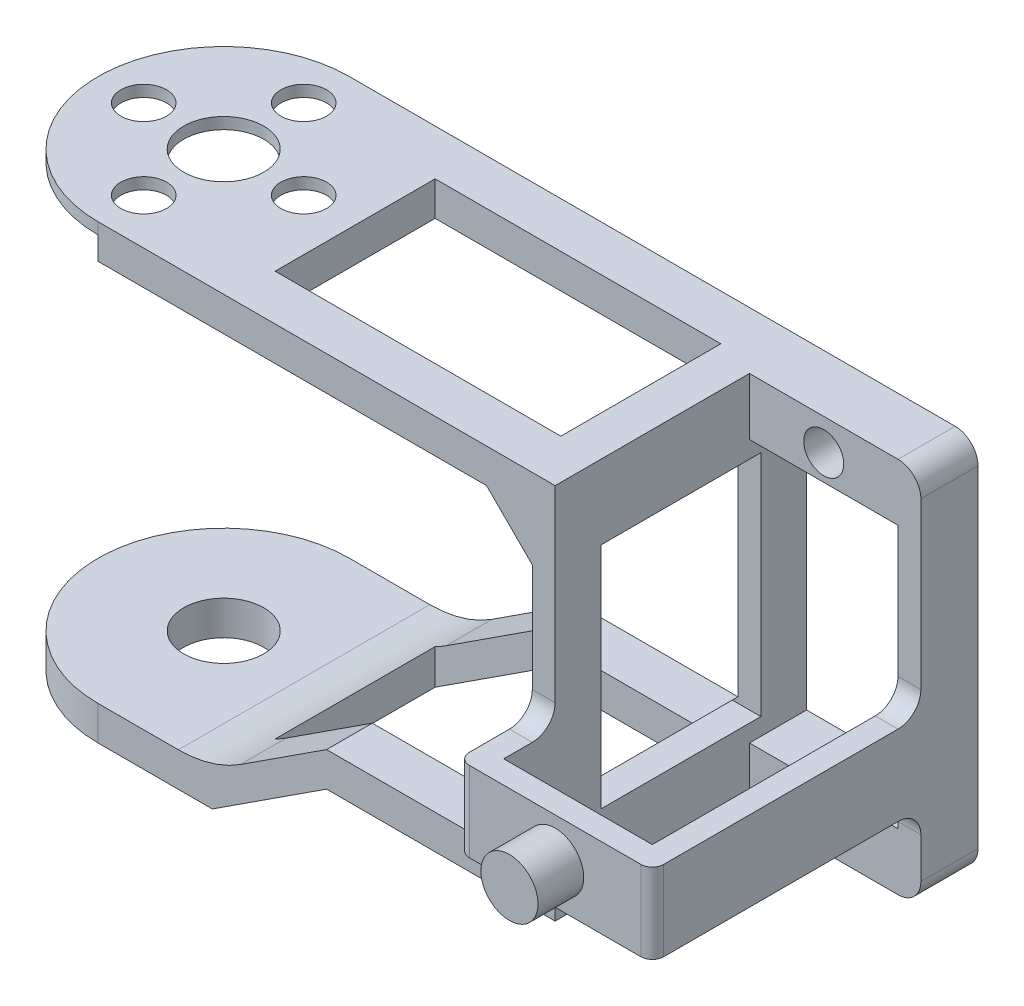
SolidWorks part; units mm, degrees
ref_plane "前视基准面" through (0, 0, 0) normal (0, 0, 1) x (1, 0, 0)
ref_plane "上视基准面" through (0, 0, 0) normal (0, 1, 0) x (1, 0, 0)
ref_plane "右视基准面" through (0, 0, 0) normal (1, 0, 0) x (0, 0, -1)
sketch "草图1" plane through (0, 0, 0) normal (0, 1, 0) x (1, 0, 0)
  line L0 (-11, 0) -> (11, 0) construction
  line L1 (0, -11) -> (0, 11) construction
  circle A1 centre (0, 0) radius 3
  circle A2 centre (-7, 0) radius 2
  circle A6 centre (0, 7) radius 2
  circle A7 centre (7, 0) radius 2
  circle A8 centre (0, -7) radius 2
  point P18 (0, 0)
  point P19 (0.1023, 0.1023)
  dimension "D1" = 7
  dimension "D2" = 6
  dimension "D3" = 4
  dimension "D4" = 4
sketch "草图2" plane through (0, 0, 0) normal (0, 1, 0) x (1, 0, 0)
  line L0 (0, -11) -> (0, 11) construction
  line L1 (0, 0) -> (67.4561, 0) construction
  line L2 (0, 11) -> (40, 11)
  line L3 (40, 11) -> (40, -11)
  line L4 (40, -11) -> (0, -11)
  arc A0 (0, -11) -> (0, 11) centre (0, 0) cw
  point P5 (40, 0)
  dimension "D1" = 11
  dimension "D4" = 40
  dimension "D3" = 11
  dimension "D2" = 11
extrude "凸台-拉伸1" add sketch "草图2" along normal blind 3
sketch "草图3" plane through (0, 0, 0) normal (0, -1, 0) x (-1, 0, 0)
  circle A0 centre (0, 0) radius 11
  dimension "D1" = 22
extrude "切除-拉伸1" cut sketch "草图3" against normal blind 2 contours A0
extrude "切除-拉伸2" cut sketch "草图1" against normal through all and the other way blind 20
ref_plane "基准面1" through (0, -33.5, 0) normal (0, -1, 0) x (-1, 0, 0)
sketch "草图4" plane through (0, -33.5, 0) normal (0, -1, 0) x (-1, 0, 0)
  line L0 (0, 0.1404) -> (0, 50000.1404) construction
  line L1 (0, 0) -> (50000, 0) construction
  line L2 (0, 11) -> (-10, 11)
  line L4 (-10, 11) -> (-10, -11)
  line L5 (-10, -11) -> (0, -11)
  line L6 (0, -11) -> (-40, -11) construction
  arc A1 (0, 11) -> (0, -11) centre (0, 0) cw
  point P0 (0, 25000.1404)
  point P1 (0, 0)
  point P3 (0, 25011.1404)
  point P8 (0, -11)
  point P9 (0, 11)
  dimension "D2" = 11
  dimension "D4" = 10
  dimension "D1" = 11
  dimension "D3" = 11
extrude "凸台-拉伸2" add sketch "草图4" along normal blind 3 separate body
sketch "草图5" plane through (0, -36.5, 0) normal (0, -1, 0) x (-1, 0, 0)
  arc A0 (0, -11) -> (0, 11) centre (0, 0) ccw construction
  circle A1 centre (0, 0) radius 3.5
  point P0 (0, 0)
  dimension "D1" = 7
extrude "切除-拉伸3" cut sketch "草图5" against normal through all
ref_plane "基准面4" through (0, -27, 0) normal (0, -1, 0) x (-1, 0, 0)
sketch "草图8" plane through (0, -27, 0) normal (0, -1, 0) x (-1, 0, 0)
  line L1 (-20, -11) -> (-40, -11)
  line L2 (-20, -11) -> (-20, 11)
  line L3 (-20, 11) -> (-40, 11)
  line L4 (-40, -11) -> (-40, 11)
  line L5 (-20, -11) -> (-40, 11) construction
  line L6 (-20, 11) -> (-40, -11) construction
  line L7 (-40, -11) -> (-40, 11) construction
  line L8 (-40, 11) -> (0, 11) construction
  line L9 (0, -11) -> (-40, -11) construction
  point P4 (-30, 0)
  dimension "D1" = 20
extrude "凸台-拉伸4" add sketch "草图8" along normal blind 3 separate body
sketch "草图10" plane through (0, 0, 0) normal (0, 0, 1) x (1, 0, 0)
  line L0 (10, -36.5) -> (20, -30)
  line L2 (20, -30) -> (20, -27)
  line L3 (20, -27) -> (10, -33.5)
  line L4 (-17.875, -33.5) -> (17.875, -33.5) construction
  line L5 (10, -36.5) -> (10, -33.5) construction
  line L6 (10, -33.5) -> (10, -36.5)
extrude "凸台-拉伸5" add sketch "草图10" along normal up to surface and the other way up to surface up to face at (30, -28.5, 11) other way up to face at (30, -28.5, -11)
ref_plane "基准面5" through (40, 0, 0) normal (1, 0, 0) x (0, 0, -1)
sketch "草图11" plane through (40, 0, 0) normal (1, 0, 0) x (0, 0, -1)
  line L0 (-11, 3) -> (11, 3) construction
  line L1 (6, 3) -> (11, 3)
  line L2 (6, 3) -> (6, -2)
  line L3 (6, -2) -> (11, -2)
  line L4 (11, 3) -> (11, -2)
  line L5 (6, 3) -> (11, -2) construction
  line L6 (6, -2) -> (11, 3) construction
  line L9 (6, -25) -> (11, -25)
  line L17 (11, 3) -> (11, 0) construction
  line L18 (6, -25) -> (6, -30)
  line L19 (6, -30) -> (11, -30)
  line L20 (11, -25) -> (11, -30)
  line L21 (6, -25) -> (11, -30) construction
  line L22 (6, -30) -> (11, -25) construction
  point P4 (8.5, 0.5)
  point P20 (8.5, -27.5)
  dimension "D1" = 5
  dimension "D2" = 0
  dimension "D3" = 5
  dimension "D4" = 23
extrude "凸台-拉伸6" add sketch "草图11" along normal blind 15 separate body
sketch "草图13" plane through (0, 3, 0) normal (0, 1, 0) x (1, 0, 0)
  line L0 (0, -11) -> (40, -11) construction
  line L1 (40, 11) -> (38, 11)
  line L2 (40, 11) -> (40, -11)
  line L3 (40, -11) -> (38, -11)
  line L4 (38, 11) -> (38, -11)
  line L5 (40, 11) -> (38, -11) construction
  line L6 (40, -11) -> (38, 11) construction
  point P4 (39, 0)
  dimension "D1" = 2
extrude "凸台-拉伸7" add sketch "草图13" against normal up to surface (33 mm away) up to face at (30, -30, 0)
ref_plane "基准面7" through (0, -13.5, 0) normal (0, -1, 0) x (-1, 0, 0)
sketch "草图14" plane through (0, 0, -6) normal (0, 0, 1) x (1, 0, 0)
  line L1 (40, 3) -> (40, -2) construction
  line L2 (-2.75, -13.5) -> (2.75, -13.5) construction
  line L4 (46.5, 0.25) -> (46.5, -27.25) construction
  circle A0 centre (46.5, 0.25) radius 1.75
  circle A1 centre (46.5, -27.25) radius 1.75
  point P0 (46.5, 0.25)
  point P11 (46.5, -27.25)
  point P12 (46.5, -13.5)
  dimension "D3" = 3.5
  dimension "D4" = 3.5
  dimension "D1" = 6.5
  dimension "D2" = 27.5
sketch "草图15" plane through (0, -2, 0) normal (0, -1, 0) x (1, 0, 0)
  line L0 (55, -11) -> (40, -11) construction
  line L1 (55, -6) -> (53, -6)
  line L2 (55, -6) -> (55, -11)
  line L3 (55, -11) -> (53, -11)
  line L4 (53, -6) -> (53, -11)
  line L5 (55, -6) -> (53, -11) construction
  line L6 (55, -11) -> (53, -6) construction
  point P4 (54, -8.5)
  dimension "D1" = 2
extrude "凸台-拉伸8" add sketch "草图15" along normal up to surface (28 mm away) up to face at (38.3333, -30, -2)
extrude "切除-拉伸4" cut sketch "草图14" against normal through all
sketch "草图16" plane through (0, 0, 11) normal (0, 0, 1) x (1, 0, 0)
  line L0 (38, -27) -> (38, 0) construction
  line L1 (38, -15.45) -> (40, -15.45)
  line L2 (38, -15.45) -> (38, -22.45)
  line L3 (38, -22.45) -> (40, -22.45)
  line L4 (40, -15.45) -> (40, -22.45)
  line L5 (38, -15.45) -> (40, -22.45) construction
  line L6 (38, -22.45) -> (40, -15.45) construction
  line L7 (40, -30) -> (40, -27) construction
  line L8 (0, 0) -> (38, 0) construction
  point P4 (39, -18.95)
  dimension "D1" = 18.95
  dimension "D2" = 7
extrude "凸台-拉伸9" add sketch "草图16" along normal blind 6.5
sketch "草图17" plane through (40, 0, 0) normal (1, 0, 0) x (0, 0, -1)
  line L0 (-17.5, -22.45) -> (-11, -22.45) construction
  line L1 (-17.5, -15.45) -> (-15.5, -15.45)
  line L2 (-17.5, -15.45) -> (-17.5, -22.45)
  line L3 (-17.5, -22.45) -> (-15.5, -22.45)
  line L4 (-15.5, -15.45) -> (-15.5, -22.45)
  line L5 (-17.5, -15.45) -> (-15.5, -22.45) construction
  line L6 (-17.5, -22.45) -> (-15.5, -15.45) construction
  point P4 (-16.5, -18.95)
  dimension "D1" = 2
extrude "凸台-拉伸10" add sketch "草图17" along normal up to surface (15 mm away) up to face at (55, -13.5, -8.5)
sketch "草图18" plane through (0, 0, 15.5) normal (0, 0, -1) x (-1, 0, 0)
  line L0 (-55, -22.45) -> (-40, -22.45) construction
  line L1 (-55, -15.45) -> (-53, -15.45)
  line L2 (-55, -15.45) -> (-55, -22.45)
  line L3 (-55, -22.45) -> (-53, -22.45)
  line L4 (-53, -15.45) -> (-53, -22.45)
  line L5 (-55, -15.45) -> (-53, -22.45) construction
  line L6 (-55, -22.45) -> (-53, -15.45) construction
  point P4 (-54, -18.95)
  point P8 (-54.7423, -22.203)
  dimension "D1" = 2
extrude "凸台-拉伸11" add sketch "草图18" along normal up to surface (21.5 mm away) up to face at (48.25, 0.25, -6)
sketch "草图19" plane through (0, 0, 17.5) normal (0, 0, 1) x (1, 0, 0)
  line L0 (55, -15.45) -> (38, -15.45) construction
  line L1 (55, -15.45) -> (55, -22.45) construction
  circle A0 centre (46.5, -18.95) radius 2.5
  point P0 (46.5, -18.95)
  dimension "D3" = 5
  dimension "D1" = 3.5
  dimension "D2" = 8.5
extrude "凸台-拉伸12" add sketch "草图19" along normal blind 4
sketch "草图20" plane through (38, 0, 0) normal (-1, 0, 0) x (0, 0, 1)
  line L0 (11, -15.45) -> (11, 0) construction
  line L1 (7, -3.5) -> (-7, -3.5)
  line L2 (7, -3.5) -> (7, -23.5)
  line L3 (7, -23.5) -> (-7, -23.5)
  line L4 (-7, -3.5) -> (-7, -23.5)
  line L5 (7, -3.5) -> (-7, -23.5) construction
  line L6 (7, -23.5) -> (-7, -3.5) construction
  line L7 (-11, 0) -> (11, 0) construction
  point P4 (0, -13.5)
  dimension "D1" = 11
  dimension "D2" = 13.5
  dimension "D3" = 14
  dimension "D4" = 20
extrude "切除-拉伸5" cut sketch "草图20" against normal up to next
sketch "草图21" plane through (0, 3, 0) normal (0, 1, 0) x (1, 0, 0)
  line L0 (55, 11) -> (0, 11) construction
  line L1 (11.5, 7) -> (36.5, 7)
  line L2 (11.5, 7) -> (11.5, -7)
  line L3 (11.5, -7) -> (36.5, -7)
  line L4 (36.5, 7) -> (36.5, -7)
  line L5 (11.5, 7) -> (36.5, -7) construction
  line L6 (11.5, -7) -> (36.5, 7) construction
  circle A0 centre (0, 0) radius 3.5 construction
  point P4 (24, 0)
  dimension "D1" = 11
  dimension "D2" = 24
  dimension "D3" = 25
  dimension "D4" = 14
extrude "切除-拉伸6" cut sketch "草图21" against normal through all
chamfer "倒角1" distance 4 angle 45 2 edges at (38, -27, 0) (38, 0, 0)
fillet "圆角1" radius 10 1 edges at (10, -33.5, 0)
fillet "圆角2" radius 2 2 edges at (55, -30, -8.5) (55, 3, -8.5)
fillet "圆角3" radius 2 4 edges at (54, -22.45, -6) (54, -15.45, -6) (39, -22.45, 11) (39, -15.45, 11)
fillet "圆角4" radius 1 2 edges at (55, -18.95, 17.5) (38, -18.95, 17.5)
